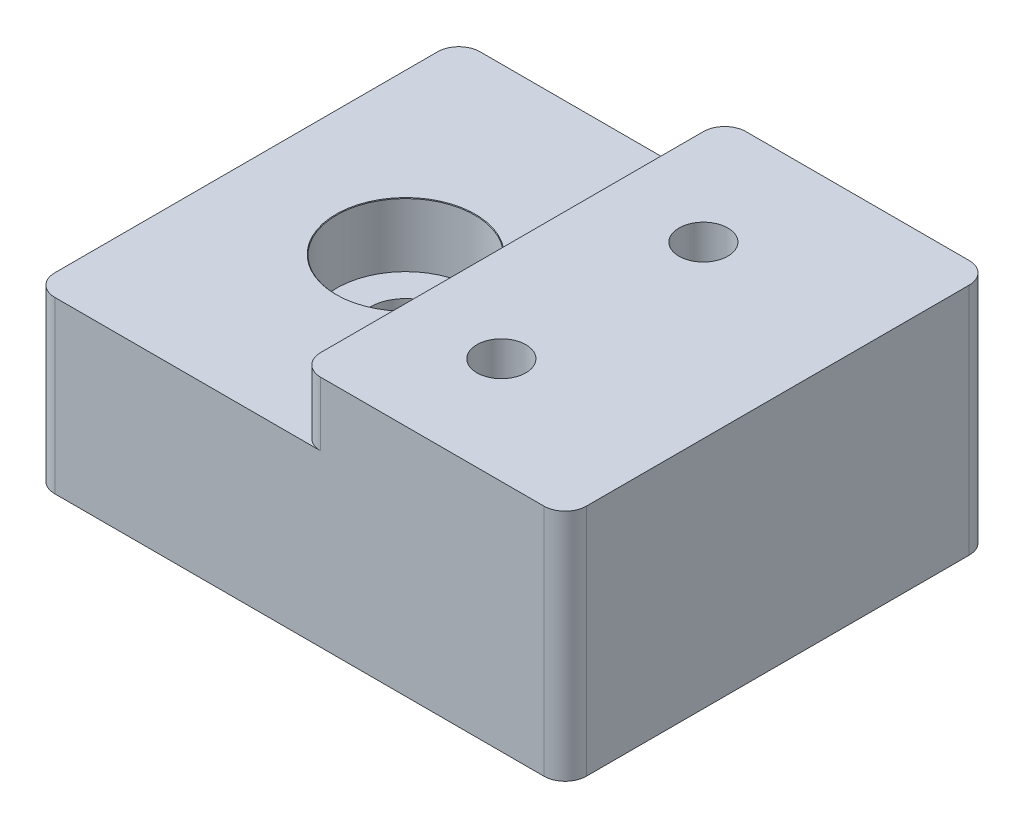
SolidWorks part; units mm, degrees
ref_plane "Front Plane" through (0, 0, 0) normal (0, 0, 1) x (1, 0, 0)
ref_plane "Top Plane" through (0, 0, 0) normal (0, 1, 0) x (1, 0, 0)
ref_plane "Right Plane" through (0, 0, 0) normal (1, 0, 0) x (0, 0, -1)
sketch "Sketch1" plane through (0, 0, 0) normal (0, 1, 0) x (1, 0, 0)
  line L1 (12.5, 10) -> (-12.5, 10)
  line L2 (12.5, 10) -> (12.5, -10)
  line L3 (12.5, -10) -> (-12.5, -10)
  line L4 (-12.5, 10) -> (-12.5, -10)
  line L5 (12.5, 10) -> (-12.5, -10) construction
  line L6 (12.5, -10) -> (-12.5, 10) construction
  point P0 (0, 0)
  dimension "D1" = 20
  dimension "D2" = 25
extrude "Boss-Extrude1" add sketch "Sketch1" along normal blind 8
sketch "Sketch2" plane through (0, 8, 0) normal (0, 1, 0) x (1, 0, 0)
  line L0 (12.5, 10) -> (-12.5, 10) construction
  line L1 (-12.5, 10) -> (-12.5, -10) construction
  point P0 (-5, 0)
  point P4 (0, 0)
  point P7 (0, 0)
  dimension "D1" = 10
  dimension "D2" = 7.5
hole_wizard "CBORE for M3 SHCS1" positions "Sketch3" profile "Sketch4" counterbore size "M3" standard "ANSI Metric" end condition through all
sketch "Sketch3" plane through (0, 8, 0) normal (0, 1, 0) x (1, 0, 0)
  point P4 (-5, 0)
  point P8 (0, 0)
sketch "Sketch4" plane through (-5, 8, 0) normal (1, 0, 0) x (0, 0, 1)
  line L0 (0, 0) -> (0, 8)
  line L1 (0, 8) -> (1.7, 8)
  line L3 (1.7, 8) -> (1.7, 3)
  line L4 (3.25, 3) -> (1.7, 3)
  line L5 (3.25, 3) -> (3.25, 0.025)
  line L6 (3.25, 0.025) -> (3.275, 0)
  line L7 (3.275, 0) -> (0, 0)
  line L8 (-3.25, 0.025) -> (-3.275, 0) construction
  line L11 (0, -6.35) -> (0, 107.95) construction
  dimension "Thru Hole Dia." = 3.4
  dimension "Thru Hole Depth" = 8
  dimension "C'Bore Dia." = 6.5
  dimension "C'Bore Depth" = 3
  dimension "Near C'Sink Dia." = 6.55
  dimension "Near C'Sink Angle" = 90
fillet "Fillet1" radius 1 4 edges at (12.5, 4, 10) (-12.5, 4, 10) (12.5, 4, -10) (-12.5, 4, -10)
sketch "Sketch5" plane through (0, 8, 0) normal (0, 1, 0) x (1, 0, 0)
  line L0 (-11.5, -10) -> (11.5, -10) construction
  line L1 (11.5, 10) -> (-11.5, 10) construction
  line L2 (12.5, -9) -> (12.5, 9) construction
  line L3 (4.5, 4.5) -> (4.5, -5) construction
  circle A0 centre (4.5, 4.5) radius 1.15
  circle A1 centre (4.5, -5) radius 1.15
  point P10 (2.1854, -5)
  dimension "D1" = 5
  dimension "D2" = 5.5
  dimension "D3" = 2.3
  dimension "D4" = 8
extrude "Cut-Extrude1" cut sketch "Sketch5" against normal blind 5
sketch "Sketch6" plane through (0, 8, 0) normal (0, 1, 0) x (1, 0, 0)
  line L0 (0, 10) -> (0, -10)
  line L1 (11.5, 10) -> (-11.5, 10) construction
  line L2 (-11.5, -10) -> (11.5, -10) construction
  line L3 (0, -10) -> (11.5, -10)
  line L4 (12.5, -9) -> (12.5, 9) construction
  line L5 (12.5, -9) -> (12.5, 9)
  line L6 (0, 10) -> (11.5, 10)
  arc A0 (12.5, 9) -> (11.5, 10) centre (11.5, 9) ccw construction
  arc A1 (11.5, -10) -> (12.5, -9) centre (11.5, -9) ccw construction
  arc A2 (12.5, 9) -> (11.5, 10) centre (11.5, 9) ccw
  arc A3 (11.5, -10) -> (12.5, -9) centre (11.5, -9) ccw
  circle A4 centre (4.5, -5) radius 1.15 construction
  circle A5 centre (4.5, 4.5) radius 1.15 construction
  circle A6 centre (4.5, -5) radius 1.15
  circle A7 centre (4.5, 4.5) radius 1.15
extrude "Boss-Extrude2" add sketch "Sketch6" along normal blind 3
fillet "Fillet2" radius 1 2 edges at (0, 9.5, 10) (0, 9.5, -10)
